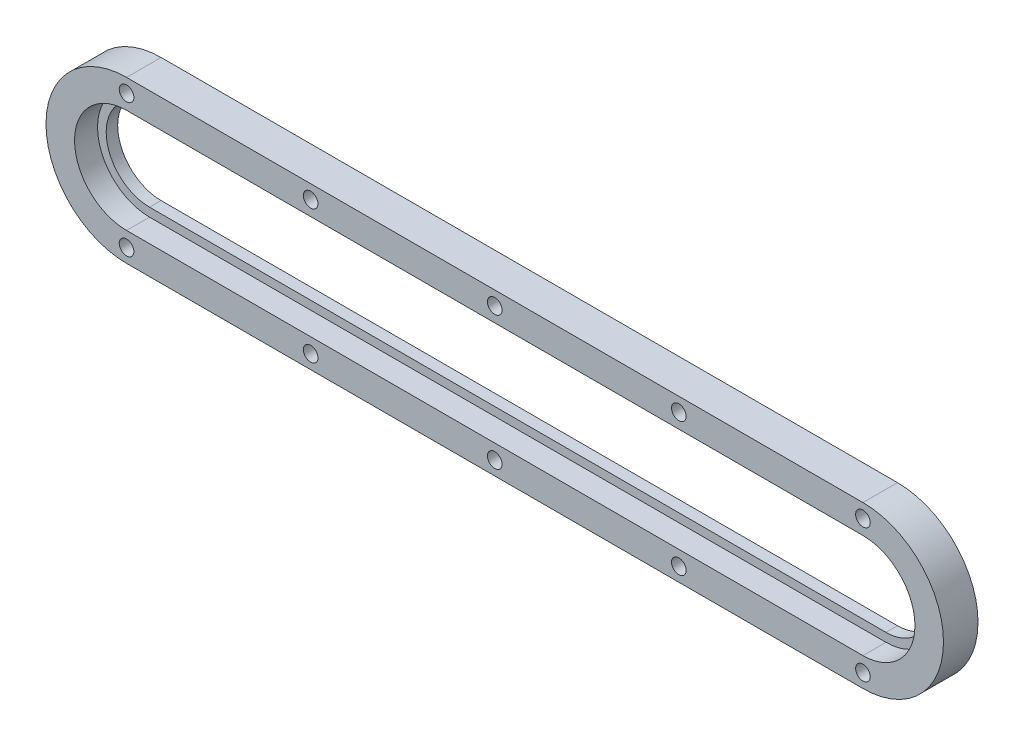
SolidWorks part; units mm, degrees
material "Nylon 101"
ref_plane "Front" through (0, 0, 0) normal (0, 0, 1) x (1, 0, 0)
ref_plane "Top" through (0, 0, 0) normal (0, 1, 0) x (1, 0, 0)
ref_plane "Right" through (0, 0, 0) normal (1, 0, 0) x (0, 0, -1)
sketch "Sketch1" plane through (0, 0, 0) normal (0, 0, 1) x (1, 0, 0)
  line L1 (123.825, 22.225) -> (-123.825, 22.225)
  line L2 (123.825, 22.225) -> (123.825, -22.225)
  line L3 (123.825, -22.225) -> (-123.825, -22.225)
  line L4 (-123.825, 22.225) -> (-123.825, -22.225)
  line L5 (123.825, 22.225) -> (-123.825, -22.225) construction
  line L6 (123.825, -22.225) -> (-123.825, 22.225) construction
  point P0 (0, 0)
  dimension "D1" = 247.65
  dimension "D2" = 44.45
extrude "Boss-Extrude1" add sketch "Sketch1" along normal blind 9.525
sketch "Sketch2" plane through (0, 0, 9.525) normal (0, 0, 1) x (1, 0, 0)
  line L0 (101.6, 0) -> (-101.6, 0) construction
  line L1 (101.6, -14.351) -> (-101.6, -14.351)
  line L2 (101.6, 14.351) -> (-101.6, 14.351)
  arc A0 (101.6, -14.351) -> (101.6, 14.351) centre (101.6, 0) ccw
  arc A1 (-101.6, 14.351) -> (-101.6, -14.351) centre (-101.6, 0) ccw
  point P2 (0, 0)
  dimension "D1" = 203.2
  dimension "D2" = 28.702
extrude "Cut-Extrude1" cut sketch "Sketch2" against normal blind 6.35
sketch "Sketch14" plane through (0, 0, 3.175) normal (0, 0, 1) x (1, 0, 0)
  line L10 (101.6, 11.9698) -> (-101.6, 11.9697)
  line L11 (-101.6, -11.9698) -> (101.6, -11.9698)
  line L12 (101.6, 11.9698) -> (-101.6, 11.9697)
  line L13 (-101.6, -11.9698) -> (101.6, -11.9698)
  arc A10 (101.6, -11.9698) -> (101.6, 11.9698) centre (101.6, 0) ccw
  arc A11 (-101.6, 11.9697) -> (-101.6, -11.9698) centre (-101.6, 0) ccw
  arc A12 (101.6, -11.9698) -> (101.6, 11.9698) centre (101.6, 0) ccw
  arc A13 (-101.6, 11.9697) -> (-101.6, -11.9698) centre (-101.6, 0) ccw
  dimension "D1" = 2.3813
extrude "Cut-Extrude3" cut sketch "Sketch14" against normal through all
sketch "Sketch3" plane through (0, 0, 9.525) normal (0, 0, 1) x (1, 0, 0)
  line L0 (-101.6, 22.225) -> (101.6, 22.225)
  line L1 (-101.6, -22.225) -> (101.6, -22.225)
  arc A2 (-101.6, 22.225) -> (-101.6, -22.225) centre (-101.6, 0) ccw
  arc A3 (-101.6, 22.225) -> (-101.6, -22.225) centre (-101.6, 0) ccw
  arc A5 (101.6, -22.225) -> (101.6, 22.225) centre (101.6, 0) ccw
  arc A6 (101.6, -22.225) -> (101.6, 22.225) centre (101.6, 0) ccw
  line M7 (-123.825, 22.225) -> (-123.825, -22.225)
  line M8 (-123.825, -22.225) -> (123.825, -22.225)
  line M9 (123.825, -22.225) -> (123.825, 22.225)
  line M10 (123.825, 22.225) -> (-123.825, 22.225)
  dimension "D1" = 7.874
  dimension "D2" = 7.874
extrude "Cut-Extrude2" cut sketch "Sketch3" against normal through all contours A3 M10 M7 | A3 M7 M8 | A6 M8 M9 | A6 M9 M10 region at (-118.8606, 17.2606, 9.525) region at (118.8606, 17.2606, 9.525) region at (-118.8606, -17.2606, 9.525) region at (118.8606, -17.2606, 9.525)
sketch "Sketch9" plane through (0, 0, 9.525) normal (0, 0, 1) x (1, 0, 0)
  line L2 (101.6, 18.415) -> (-101.6, 18.415)
  line L3 (101.6, 18.415) -> (-101.6, 18.415) construction
  line L4 (-101.6, 18.415) -> (0, 18.415) construction
  line L5 (-101.6, -18.415) -> (101.6, -18.415)
  line L6 (-101.6, -18.415) -> (101.6, -18.415) construction
  line L7 (0, 18.415) -> (101.6, 18.415) construction
  line L8 (-101.6, -18.415) -> (0, -18.415) construction
  line L9 (0, -18.415) -> (101.6, -18.415) construction
  point P0 (0, 18.415)
  point P1 (-101.6, 18.415)
  point P6 (0, -18.415)
  point P7 (101.6, 18.415)
  point P8 (101.6, -18.415)
  point P9 (-50.8, 18.415)
  point P10 (-101.6, -18.415)
  point P13 (-50.8, -18.415)
  point P14 (50.8, 18.415)
  point P15 (50.8, -18.415)
  point P16 (0, 0)
  dimension "D1" = 4.064
  dimension "D2" = 4.064
hole_wizard "#10-32 Tapped Hole1" positions "Sketch10" profile "Sketch11" tap size "#10-32" standard "ANSI Inch" end condition through all
sketch "Sketch10" plane through (0, 0, 9.525) normal (0, 0, 1) x (1, 0, 0)
  point P0 (-101.6, 18.415)
  point P3 (-50.8, 18.415)
  point P6 (0, 18.415)
  point P9 (50.8, 18.415)
  point P12 (101.6, 18.415)
  point P15 (101.6, -18.415)
  point P18 (50.8, -18.415)
  point P21 (0, -18.415)
  point P24 (-50.8, -18.415)
  point P27 (-101.6, -18.415)
sketch "Sketch11" plane through (-101.6, 18.415, 9.525) normal (1, 0, 0) x (0, -1, 0)
  line L0 (0, 0) -> (0, 9.525)
  line L1 (0, 9.525) -> (2.0193, 9.525)
  line L2 (2.0193, 9.525) -> (2.0193, 0)
  line L5 (2.0193, 0) -> (0, 0)
  line L11 (0, -6.35) -> (0, 107.95) construction
  dimension "Thru Tap Drill Dia." = 4.0386
  dimension "Thru Tap Drill Depth" = 9.525
cosmetic thread "Hole Thread1" parameters "D2"=4.826
cosmetic thread "Hole Thread2" parameters "D2"=4.826
cosmetic thread "Hole Thread3" parameters "D2"=4.826
cosmetic thread "Hole Thread4" parameters "D2"=4.826
cosmetic thread "Hole Thread5" parameters "D2"=4.826
cosmetic thread "Hole Thread6" parameters "D2"=4.826
cosmetic thread "Hole Thread7" parameters "D2"=4.826
cosmetic thread "Hole Thread8" parameters "D2"=4.826
cosmetic thread "Hole Thread9" parameters "D2"=4.826
cosmetic thread "Hole Thread10" parameters "D2"=4.826
